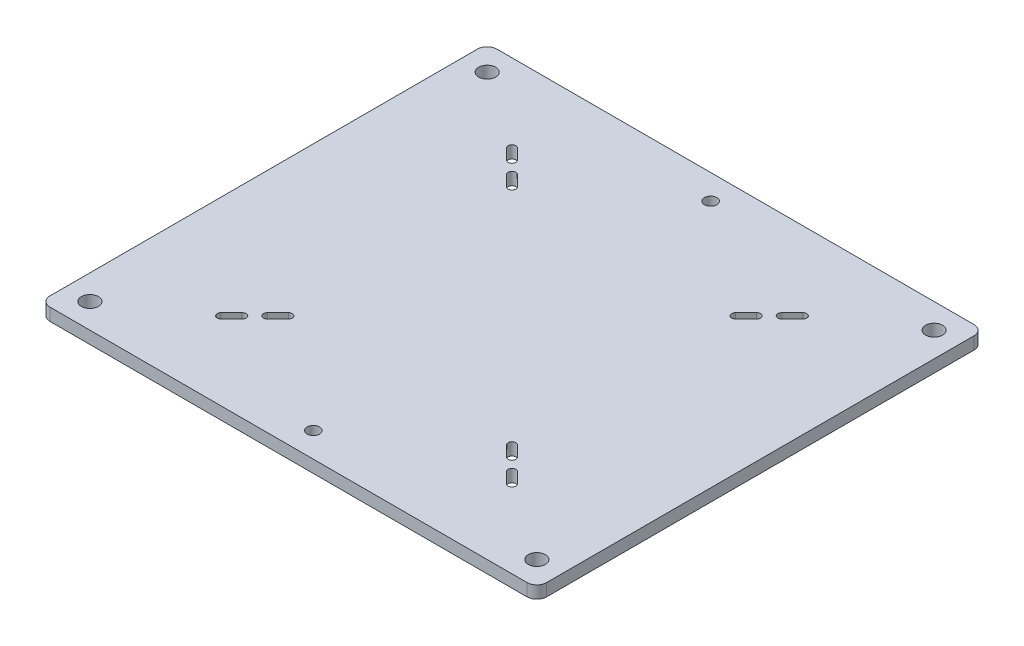
SolidWorks part; units mm, degrees
ref_plane "Front Plane" through (0, 0, 0) normal (0, 0, 1) x (1, 0, 0)
ref_plane "Top Plane" through (0, 0, 0) normal (0, 1, 0) x (1, 0, 0)
ref_plane "Right Plane" through (0, 0, 0) normal (1, 0, 0) x (0, 0, -1)
sketch "Sketch1" plane through (0, 0, 0) normal (0, 1, 0) x (1, 0, 0)
  line L1 (0, 0) -> (254, 0)
  line L2 (0, 0) -> (0, -228.6)
  line L3 (0, -228.6) -> (254, -228.6)
  line L4 (254, 0) -> (254, -228.6)
  dimension "D1" = 254
  dimension "D2" = 228.6
extrude "base plate" add sketch "Sketch1" against normal blind 6.35
sketch "center lines" plane through (0, 0, 0) normal (0, 1, 0) x (1, 0, 0)
  line L0 (127, 0) -> (127, -228.6) construction
  line L1 (254, 0) -> (0, 0) construction
  line L2 (0, -228.6) -> (254, -228.6) construction
  line L3 (0, -114.3) -> (254, -114.3) construction
  line L4 (0, 0) -> (0, -228.6) construction
  line L5 (254, -228.6) -> (254, 0) construction
sketch "Sketch3" plane through (0, 0, 0) normal (0, 1, 0) x (1, 0, 0)
  line L0 (42.875, -187.6487) -> (53.6513, -198.425)
  line L1 (53.6513, -198.425) -> (87.7763, -164.3)
  line L2 (87.7763, -164.3) -> (77, -153.5237)
  line L3 (77, -153.5237) -> (42.875, -187.6487)
  line L4 (52.619, -188.681) -> (58.0071, -183.2929) construction
  line L5 (51.2047, -187.2668) -> (56.5929, -181.8787)
  line L6 (54.0332, -190.0953) -> (59.4213, -184.7071)
  line L7 (0, -228.6) -> (254, -228.6) construction
  line L8 (69.8158, -171.4842) -> (64.4276, -176.8724) construction
  line L9 (71.23, -172.8984) -> (65.8419, -178.2866)
  line L10 (127, 0) -> (127, -228.6) construction
  line L11 (0, -114.3) -> (254, -114.3) construction
  line L12 (87.7763, -64.3) -> (77, -75.0763)
  line L13 (53.6513, -30.175) -> (87.7763, -64.3)
  line L14 (42.875, -40.9513) -> (53.6513, -30.175)
  line L15 (77, -75.0763) -> (42.875, -40.9513)
  line L16 (200.3487, -30.175) -> (166.2237, -64.3)
  line L17 (211.125, -40.9513) -> (200.3487, -30.175)
  line L18 (177, -75.0763) -> (211.125, -40.9513)
  line L19 (166.2237, -64.3) -> (177, -75.0763)
  line L20 (166.2237, -164.3) -> (177, -153.5237)
  line L21 (200.3487, -198.425) -> (166.2237, -164.3)
  line L22 (211.125, -187.6487) -> (200.3487, -198.425)
  line L23 (177, -153.5237) -> (211.125, -187.6487)
  line L24 (68.4016, -170.07) -> (63.0134, -175.4581)
  line L25 (52.619, -39.919) -> (58.0071, -45.3071) construction
  line L26 (51.2047, -41.3332) -> (56.5929, -46.7213)
  line L27 (54.0332, -38.5047) -> (59.4213, -43.8929)
  line L28 (69.8158, -57.1158) -> (64.4276, -51.7276) construction
  line L29 (71.23, -55.7016) -> (65.8419, -50.3134)
  line L30 (68.4016, -58.53) -> (63.0134, -53.1419)
  line L31 (201.381, -39.919) -> (195.9929, -45.3071) construction
  line L32 (202.7953, -41.3332) -> (197.4071, -46.7213)
  line L33 (199.9668, -38.5047) -> (194.5787, -43.8929)
  line L34 (184.1842, -57.1158) -> (189.5724, -51.7276) construction
  line L35 (182.77, -55.7016) -> (188.1581, -50.3134)
  line L36 (185.5984, -58.53) -> (190.9866, -53.1419)
  line L37 (184.1842, -171.4842) -> (189.5724, -176.8724) construction
  line L38 (182.77, -172.8984) -> (188.1581, -178.2866)
  line L39 (185.5984, -170.07) -> (190.9866, -175.4581)
  line L40 (201.381, -188.681) -> (195.9929, -183.2929) construction
  line L41 (202.7953, -187.2668) -> (197.4071, -181.8787)
  line L42 (199.9668, -190.0953) -> (194.5787, -184.7071)
  line L43 (77, -164.3) -> (77, -153.5237)
  line L44 (87.7763, -164.3) -> (77, -164.3)
  line L45 (77, -64.3) -> (77, -75.0763)
  line L46 (87.7763, -64.3) -> (77, -64.3)
  line L47 (177, -64.3) -> (177, -75.0763)
  line L48 (166.2237, -64.3) -> (177, -64.3)
  line L49 (177, -164.3) -> (177, -153.5237)
  line L50 (166.2237, -164.3) -> (177, -164.3)
  arc A0 (51.2047, -187.2668) -> (54.0332, -190.0953) centre (52.619, -188.681) ccw
  arc A1 (59.4213, -184.7071) -> (56.5929, -181.8787) centre (58.0071, -183.2929) ccw
  arc A2 (71.23, -172.8984) -> (68.4016, -170.07) centre (69.8158, -171.4842) ccw
  arc A3 (63.0134, -175.4581) -> (65.8419, -178.2866) centre (64.4276, -176.8724) ccw
  arc A4 (51.2047, -41.3332) -> (54.0332, -38.5047) centre (52.619, -39.919) cw
  arc A5 (59.4213, -43.8929) -> (56.5929, -46.7213) centre (58.0071, -45.3071) cw
  arc A6 (71.23, -55.7016) -> (68.4016, -58.53) centre (69.8158, -57.1158) cw
  arc A7 (63.0134, -53.1419) -> (65.8419, -50.3134) centre (64.4276, -51.7276) cw
  arc A8 (202.7953, -41.3332) -> (199.9668, -38.5047) centre (201.381, -39.919) ccw
  arc A9 (194.5787, -43.8929) -> (197.4071, -46.7213) centre (195.9929, -45.3071) ccw
  arc A10 (182.77, -55.7016) -> (185.5984, -58.53) centre (184.1842, -57.1158) ccw
  arc A11 (190.9866, -53.1419) -> (188.1581, -50.3134) centre (189.5724, -51.7276) ccw
  arc A12 (182.77, -172.8984) -> (185.5984, -170.07) centre (184.1842, -171.4842) cw
  arc A13 (190.9866, -175.4581) -> (188.1581, -178.2866) centre (189.5724, -176.8724) cw
  arc A14 (202.7953, -187.2668) -> (199.9668, -190.0953) centre (201.381, -188.681) cw
  arc A15 (194.5787, -184.7071) -> (197.4071, -181.8787) centre (195.9929, -183.2929) cw
  point P29 (55.313, -185.987)
  point P36 (67.1217, -174.1783)
  point P44 (55.313, -42.613)
  point P51 (67.1217, -54.4217)
  point P58 (198.687, -42.613)
  point P65 (186.8783, -54.4217)
  point P72 (186.8783, -174.1783)
  point P79 (198.687, -185.987)
  point P84 (59.4213, -181.8787)
  point P85 (63.0134, -178.2866)
  dimension "D6" = 2
  dimension "D10" = 5.08
  dimension "D9" = 10.16
  dimension "D1" = 48.26
  dimension "D2" = 15.24
  dimension "D3" = 45
  dimension "D4" = 100
  dimension "D5" = 100
  dimension "D7" = 7.62
  dimension "D8" = 7.62
extrude "slots" cut sketch "Sketch3" against normal through all contours A5 L27 A4 L26 | L33 A9 L32 A8 | L36 A11 L35 A10 | A13 L39 A12 L38 | A15 L42 A14 L41 | L6 A1 L5 A0 | L24 A3 L9 A2 | L30 A7 L29 A6 region at (55.313, 0, 42.613) region at (198.687, 0, 42.613) region at (186.8783, 0, 54.4217) region at (186.8783, 0, 174.1783) region at (198.687, 0, 185.987)
hole_wizard "Feet connection hole" positions "Sketch6" profile "Sketch7" hole size "1/4-20" standard "PEM® Inch" end condition through all
sketch "Sketch6" plane through (0, 0, 0) normal (0, 1, 0) x (1, 0, 0)
  line L0 (0, -228.6) -> (254, -228.6) construction
  line L1 (0, 0) -> (0, -228.6) construction
  line L2 (254, -228.6) -> (254, 0) construction
  line L3 (254, 0) -> (0, 0) construction
  point P3 (12.7, -215.9)
  point P19 (241.3, -12.7)
  point P33 (12.7, -12.7)
  point P37 (241.3, -215.9)
  dimension "D1" = 12.7
  dimension "D2" = 12.7
  dimension "D3" = 12.7
  dimension "D4" = 12.7
sketch "Sketch7" plane through (12.7, 0, 215.9) normal (1, 0, 0) x (0, 0, 1)
  line L0 (0, 0) -> (0, 6.35)
  line L1 (0, 6.35) -> (4.3688, 6.35)
  line L2 (4.3688, 6.35) -> (4.3688, 0)
  line L5 (4.3688, 0) -> (0, 0)
  line L11 (0, -6.35) -> (0, 107.95) construction
  dimension "Thru Hole Dia." = 8.7376
  dimension "Thru Hole Depth" = 6.35
hole_wizard "Hole for #10 Blind Fasteners (B,BS)1" positions "Sketch17" profile "Sketch18" hole size "#10-32" standard "PEM® Inch" end condition through all
sketch "Sketch17" plane through (0, 0, 0) normal (0, 1, 0) x (1, 0, 0)
  line L0 (0, -228.6) -> (254, -228.6) construction
  line L1 (254, 0) -> (0, 0) construction
  line L2 (254, -228.6) -> (254, 0) construction
  line L3 (0, 0) -> (0, -228.6) construction
  point P0 (127, -215.9)
  point P2 (127, -12.7)
  dimension "D1" = 12.7
  dimension "D2" = 12.7
  dimension "D3" = 127
  dimension "D4" = 127
sketch "Sketch18" plane through (127, 0, 215.9) normal (1, 0, 0) x (0, 0, 1)
  line L0 (0, 0) -> (0, 6.35)
  line L1 (0, 6.35) -> (3.175, 6.35)
  line L2 (3.175, 6.35) -> (3.175, 0)
  line L5 (3.175, 0) -> (0, 0)
  line L11 (0, -6.35) -> (0, 107.95) construction
  dimension "Thru Hole Dia." = 6.35
  dimension "Thru Hole Depth" = 6.35
fillet "Fillet1" radius 5 4 edges at (0, -3.175, 0) (0, -3.175, 228.6) (254, -3.175, 228.6) (254, -3.175, 0)
